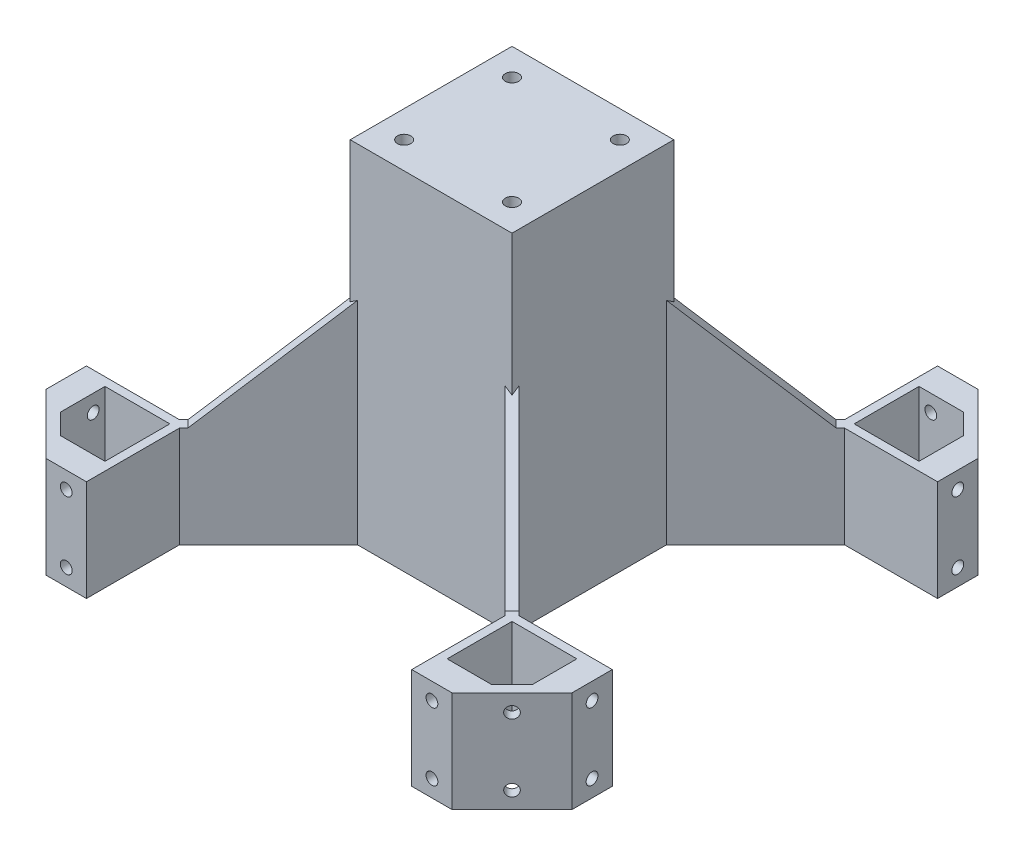
SolidWorks part; units mm, degrees
ref_plane "Front Plane" through (0, 0, 0) normal (0, 0, 1) x (1, 0, 0)
ref_plane "Top Plane" through (0, 0, 0) normal (0, 1, 0) x (1, 0, 0)
ref_plane "Right Plane" through (0, 0, 0) normal (1, 0, 0) x (0, 0, -1)
sketch "Sketch1" plane through (0, 0, 0) normal (0, 1, 0) x (1, 0, 0)
  line L0 (0, 0) -> (0, -80) construction
  line L1 (0, 0) -> (80, 0) construction
  line L2 (0, -78) -> (59.25, -78) construction
  line L7 (59.25, -78) -> (59.25, -82) construction
  line L8 (78, 0) -> (78, -59.25) construction
  line L9 (78, -59.25) -> (82, -59.25) construction
  line L10 (48.25, -78) -> (48.25, -50.3713)
  line L11 (48.25, -78) -> (60.25, -78)
  line L12 (60.25, -78) -> (69.125, -69.125)
  line L15 (0, 0) -> (110.9515, -110.9515) construction
  line L16 (48.25, -50.3713) -> (20.1525, -22.2739)
  line L18 (50.75, -50.75) -> (50.75, -70)
  line L19 (50.75, -70) -> (64.0074, -70)
  line L20 (64.0074, -70) -> (67.0037, -67.0037)
  line L21 (67.0037, -67.0037) -> (69.125, -69.125)
  line L22 (50.75, -50.75) -> (21.2132, -21.2132)
  line L23 (21.2132, -21.2132) -> (20.1525, -22.2739)
  circle A0 centre (0, -80) radius 47.5 construction
  circle A1 centre (0, -80) radius 55 construction
  circle A2 centre (80, 0) radius 55 construction
  circle A3 centre (80, 0) radius 47.5 construction
  point P12 (54.25, -78)
  point P14 (78, -54.25)
  point P21 (20.4565, -22.4862)
  dimension "D1" = 95
  dimension "D2" = 110
  dimension "D3" = 110
  dimension "D4" = 80
  dimension "D5" = 2
  dimension "D6" = 2
  dimension "D7" = 4
  dimension "D8" = 4
  dimension "D9" = 59.25
  dimension "D10" = 54.25
  dimension "D11" = 54.25
  dimension "D12" = 45
  dimension "D13" = 2.5
  dimension "D14" = 12
  dimension "D15" = 8
  dimension "D16" = 3
  dimension "D17" = 1.5
  dimension "D18" = 30
extrude "Boss-Extrude1" add sketch "Sketch1" along normal blind 30
sketch "Sketch2" plane through (0, 0, 78) normal (0, 0, 1) x (1, 0, 0)
  line L0 (0, 0) -> (0, 86.05) construction
  line L1 (48.25, 0) -> (60.25, 0) construction
  circle A0 centre (54.25, 5) radius 1.75
  circle A1 centre (54.25, 25) radius 1.75
  point P7 (0, 0)
  dimension "D2" = 3.5
  dimension "D1" = 54.25
  dimension "D3" = 20
  dimension "D4" = 5
extrude "Cut-Extrude1" cut sketch "Sketch2" against normal up to surface (8 mm away) up to face at (57.3787, 15, 70)
ref_axis "Axis1" through (0, 31.5, 0) along (0, -1, 0)
mirror "Mirror1" about plane through (50.75, 30, 50.75) normal (-0.7071, 0, 0.7071) of "Boss-Extrude1", "Cut-Extrude1"
sketch "Sketch5" plane through (69.125, 0, 69.125) normal (0.7071, 0, 0.7071) x (0.7071, 0, -0.7071)
  line L0 (-12.5511, 0) -> (12.5511, 0) construction
  line L1 (0, 0) -> (0, 47.4993) construction
  circle A0 centre (0, 25) radius 1.75
  circle A1 centre (0, 5) radius 1.75
  point P4 (0, 24.8612)
  dimension "D3" = 3.5
  dimension "D1" = 20
  dimension "D2" = 5
extrude "Cut-Extrude2" cut sketch "Sketch5" against normal up to surface (3 mm away) up to face at (67.0037, 15, 67.0037)
sketch "Sketch3" plane through (-1.0607, 0, 1.0607) normal (-0.7071, 0, 0.7071) x (0.7071, 0, 0.7071)
  line L0 (30, 30) -> (30, 65)
  line L1 (30, 65) -> (68, 30)
  line L2 (30, 30) -> (69.7358, 30) construction
  line L3 (68, 30) -> (30, 30)
  dimension "D1" = 38
  dimension "D2" = 35
extrude "Boss-Extrude2" add sketch "Sketch3" against normal up to surface (3 mm away) up to face at (36.3226, 15, 34.2013)
pattern_circular "CirPattern5" count 4 every 90 about axis through (0, 31.5, 0) along (0, -1, 0) of bodies 108 102
sketch "Sketch4" plane through (0, 0, 0) normal (0, -1, 0) x (1, 0, 0)
  line L1 (-24, -24) -> (24, -24)
  line L2 (-24, -24) -> (-24, 24)
  line L3 (-24, 24) -> (24, 24)
  line L4 (24, -24) -> (24, 24)
  line L5 (-24, -24) -> (24, 24) construction
  line L6 (-24, 24) -> (24, -24) construction
  line L7 (-21, -21) -> (21, -21)
  line L8 (-21, -21) -> (-21, 21)
  line L9 (-21, 21) -> (21, 21)
  line L10 (21, -21) -> (21, 21)
  line L11 (-21, -21) -> (21, 21) construction
  line L12 (-21, 21) -> (21, -21) construction
  point P0 (0, 0)
  point P6 (0, 0)
  point P11 (21.6686, 21.0813)
  dimension "D1" = 48
  dimension "D2" = 3
extrude "Boss-Extrude3" add sketch "Sketch4" against normal blind 100
sketch "Sketch6" plane through (0, 100, 0) normal (0, 1, 0) x (1, 0, 0)
  line L5 (24, -24) -> (24, 24)
  line L6 (24, 24) -> (-24, 24)
  line L7 (-24, 24) -> (-24, -24)
  line L8 (-24, -24) -> (24, -24)
  line L9 (24, -24) -> (24, 24)
  line L10 (24, 24) -> (-24, 24)
  line L11 (-24, 24) -> (-24, -24)
  line L12 (-24, -24) -> (24, -24)
  dimension "D1" = 0
extrude "Boss-Extrude4" add sketch "Sketch6" along normal blind 3
sketch "Sketch7" plane through (0, 103, 0) normal (0, 1, 0) x (1, 0, 0)
  line L1 (16, -16) -> (-16, -16) construction
  line L2 (16, -16) -> (16, 16) construction
  line L3 (16, 16) -> (-16, 16) construction
  line L4 (-16, -16) -> (-16, 16) construction
  line L5 (16, -16) -> (-16, 16) construction
  line L6 (16, 16) -> (-16, -16) construction
  circle A0 centre (16, 16) radius 2
  circle A1 centre (-16, 16) radius 2
  circle A2 centre (-16, -16) radius 2
  circle A3 centre (16, -16) radius 2
  point P0 (-18.2858, -16.0312)
  point P8 (0, 0)
  point P9 (18.2858, 16.0292)
  dimension "D1" = 4
  dimension "D2" = 32
  dimension "D3" = 32
extrude "Cut-Extrude3" cut sketch "Sketch7" against normal up to surface (3 mm away) up to face at (0, 100, 0)
